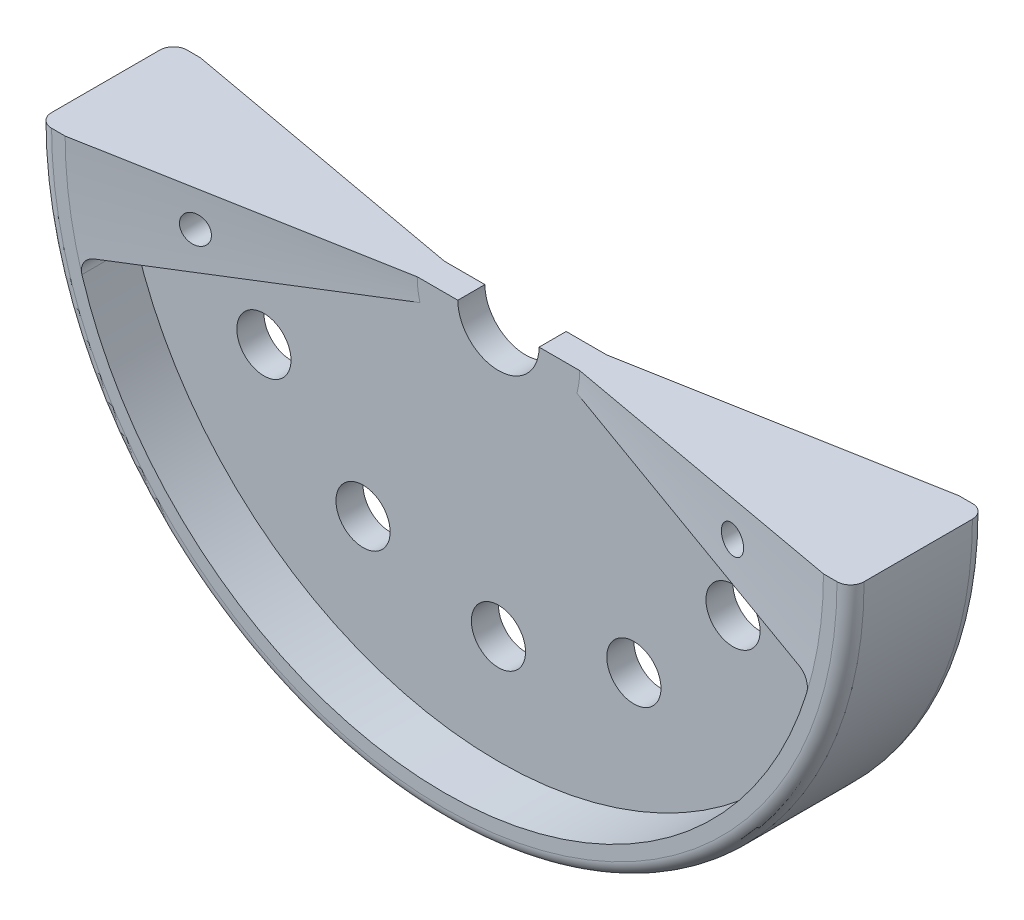
SolidWorks part; units mm, degrees
material "PS Medium/High Flow"
ref_plane "Front Plane" through (0, 0, 0) normal (0, 0, 1) x (1, 0, 0)
ref_plane "Top Plane" through (0, 0, 0) normal (0, 1, 0) x (1, 0, 0)
ref_plane "Right Plane" through (0, 0, 0) normal (1, 0, 0) x (0, 0, -1)
sketch "Sketch1" plane through (0, 0, 0) normal (0, 1, 0) x (1, 0, 0)
  line L0 (0, 1.27) -> (0, -1.27) construction
  line L1 (0, -1.27) -> (-3.81, -1.27) construction
  line L2 (0, 1.27) -> (-3.81, 1.27) construction
  line L3 (-3.81, 1.27) -> (-3.81, -1.27)
  line L4 (-3.81, -1.27) -> (-35.56, -1.27)
  line L5 (-35.56, -1.27) -> (-35.56, -6.35)
  line L6 (-35.56, -6.35) -> (-38.1, -6.35)
  line L7 (-38.1, -6.35) -> (-38.1, 6.35)
  line L8 (-38.1, 6.35) -> (-35.56, 6.35)
  line L9 (-35.56, 6.35) -> (-35.56, 1.27)
  line L10 (-35.56, 1.27) -> (-3.81, 1.27)
  point P11 (0, 0)
  point P12 (0, 0)
  point P13 (-38.1, 0)
  point P14 (-3.81, 0)
  dimension "D1" = 12.7
  dimension "D2" = 2.54
  dimension "D3" = 2.54
  dimension "D4" = 3.81
  dimension "D5" = 38.1
revolve "Revolve1" add sketch "Sketch1" angle 180 about L0
sketch "Sketch3" plane through (0, 0, 0) normal (0, 1, 0) x (1, 0, 0)
  line L0 (-35.56, 6.35) -> (-35.56, 1.27)
  line L1 (-35.56, 1.27) -> (-7.62, 1.27)
  line L2 (-3.81, 1.27) -> (-35.56, 1.27) construction
  line L3 (-7.62, 1.27) -> (-35.56, 6.35)
  line L4 (-3.81, -1.27) -> (-3.81, 1.27) construction
  line L5 (0, 0) -> (0, 5.0282) construction
  dimension "D1" = 3.81
revolve "Revolve2" add sketch "Sketch3" angle 15 about L5 region at (-26.2467, 0, -2.9633) reverse direction yes
mirror "Mirror1" about plane through (0, 0, 0) normal (1, 0, 0) of "Revolve2"
mirror "Mirror2" about plane through (0, 0, 0) normal (0, 0, 1) of "Mirror1"
sketch "Sketch4" plane through (0, 0, 0) normal (0, 0, 1) x (1, 0, 0)
  line L0 (0, 0) -> (-40.5849, -5.3431) construction
  line L1 (0, 0) -> (0, -42.3665) construction
  line L2 (0, 0) -> (-36.7388, -21.2112) construction
  line L3 (0, 0) -> (-20.7922, -36.0131) construction
  line L4 (0, 0) -> (43.2718, -5.6968) construction
  line L5 (0, 0) -> (37.7932, -21.8199) construction
  line L6 (0, 0) -> (25.4, -43.9941) construction
  line L7 (-7.62, 0) -> (-35.56, 0) construction
  line L8 (7.62, 0) -> (35.56, 0) construction
  circle A0 centre (0, 0) radius 25.4 construction
  circle A1 centre (-25.1827, -3.3154) radius 1.27
  circle A2 centre (-21.997, -12.7) radius 2.54
  circle A3 centre (-12.7, -21.997) radius 2.54
  circle A4 centre (0, -25.4) radius 2.54
  circle A5 centre (12.7, -21.997) radius 2.54
  circle A6 centre (21.997, -12.7) radius 2.54
  circle A7 centre (25.1827, -3.3154) radius 1.27
  point P28 (0, 0)
  point P29 (0, 0)
  point P30 (0, 0)
  point P31 (0, 0)
  point P32 (0, 0)
  point P33 (0, 0)
  point P34 (0, 0)
  dimension "D1" = 50.8
  dimension "D8" = 2.54
  dimension "D9" = 5.08
  dimension "D2" = 7.5
  dimension "D3" = 7.5
  dimension "D4" = 30
  dimension "D5" = 30
  dimension "D6" = 30
  dimension "D7" = 30
extrude "Cut-Extrude1" cut sketch "Sketch4" against normal through all both and the other way through all
fillet "Fillet1" radius 1.27 2 edges at (0, -38.1, -6.35) (0, -38.1, 6.35)
fillet "Fillet2" radius 1.27 4 edges at (-34.3483, -9.2036, 3.81) (34.3483, -9.2036, 3.81) (34.3483, -9.2036, -3.81) (-34.3483, -9.2036, -3.81)
